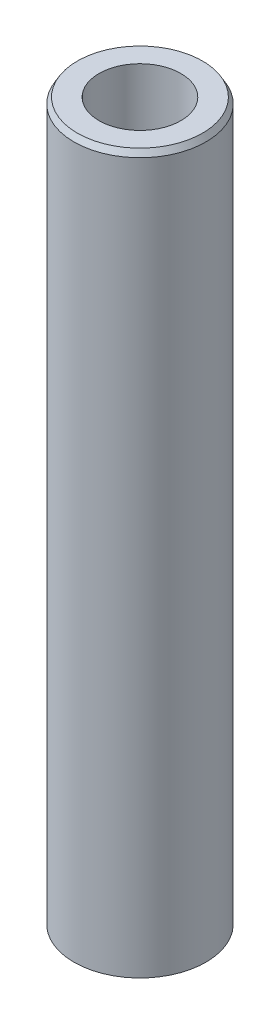
SolidWorks part; units mm, degrees
ref_plane "Front Plane" through (0, 0, 0) normal (0, 0, 1) x (1, 0, 0)
ref_plane "Top Plane" through (0, 0, 0) normal (0, 1, 0) x (1, 0, 0)
ref_plane "Right Plane" through (0, 0, 0) normal (1, 0, 0) x (0, 0, -1)
sketch "Sketch1" plane through (0, 0, 0) normal (0, 1, 0) x (1, 0, 0)
  circle A0 centre (0, 0) radius 55
  dimension "SHAFT_OD" = 110
extrude "Boss-Extrude1" add sketch "Sketch1" along normal blind 600
sketch "Sketch2" plane through (0, 0, 0) normal (0, 1, 0) x (1, 0, 0)
  circle A0 centre (0, 0) radius 34.1091
  dimension "BORE_D" = 68.2181
extrude "Cut-Extrude1" cut sketch "Sketch2" along normal through all
chamfer "Chamfer1" distance 4.9225 angle 30 2 edges at (0, 600, 55) (0, 0, 55) first distance on face at (0, 600, 55) first distance on face at (0, 0, 34.1091)
